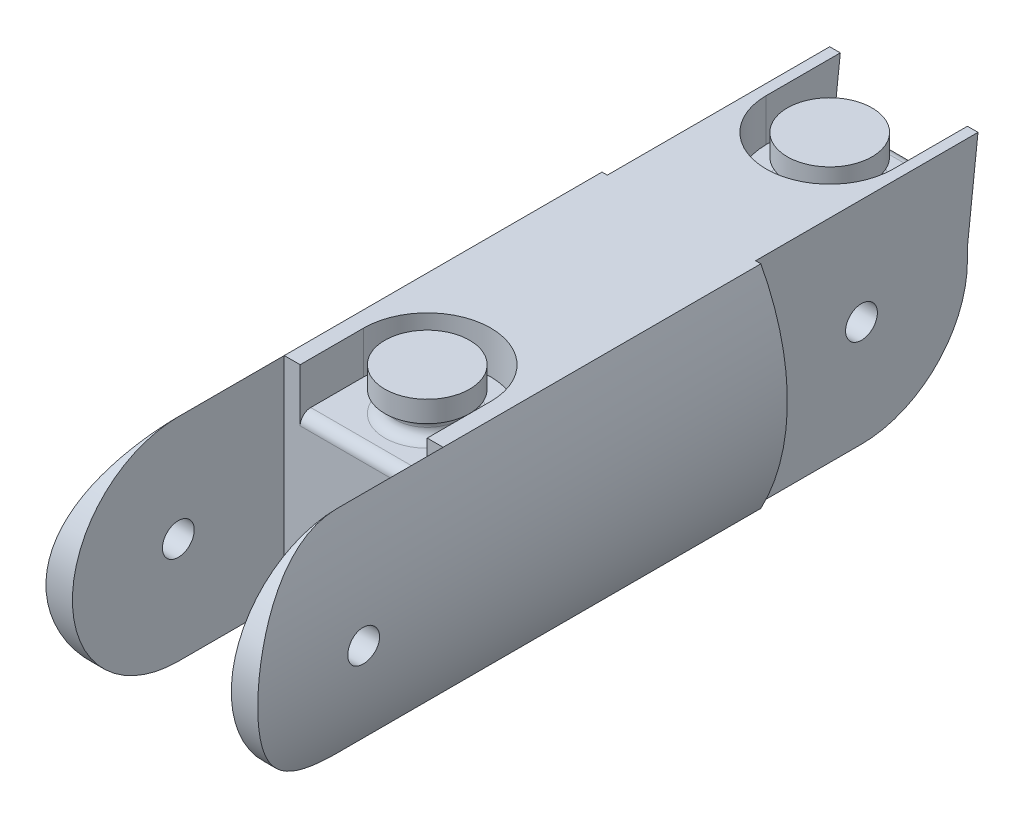
SolidWorks part; units mm, degrees
ref_plane "Alzado" through (0, 0, 0) normal (0, 0, 1) x (1, 0, 0)
ref_plane "Planta" through (0, 0, 0) normal (0, 1, 0) x (1, 0, 0)
ref_plane "Vista lateral" through (0, 0, 0) normal (1, 0, 0) x (0, 0, -1)
sketch "Croquis2" plane through (0, 0, 0) normal (0, 0, 1) x (1, 0, 0)
  line L5 (-7.5, -10) -> (7.5, -10)
  line L7 (-7.5, 10) -> (7.5, 10)
  line L9 (-7.5, -10) -> (7.5, 10) construction
  line L10 (-7.5, 10) -> (7.5, -10) construction
  arc A2 (-7.5, 10) -> (-7.5, -10) centre (11.25, 0) ccw
  arc A3 (7.5, -10) -> (7.5, 10) centre (-11.25, 0) ccw
  point P0 (0, 0)
  dimension "D1" = 15
  dimension "D2" = 20
extrude "Saliente-Extruir2" add sketch "Croquis2" along normal blind 50
sketch "Croquis4" plane through (0, 0, 0) normal (0, 0, -1) x (-1, 0, 0)
  line L1 (7.5, -10) -> (-7.5, -10) construction
  circle A0 centre (0, -7) radius 1.5
  dimension "D2" = 3
  dimension "D1" = 3
extrude "Cortar-Extruir1" cut sketch "Croquis4" against normal blind 50
sketch "Croquis3" plane through (0, 0, 0) normal (0, 0, -1) x (-1, 0, 0)
  line L8 (7.5, -10) -> (-7.5, -10) construction
  line L10 (7, 10) -> (7, -10)
  line L11 (7, -10) -> (3, -10)
  line L12 (-7, 10) -> (-7, -10)
  line L13 (7, 10) -> (-7, -10) construction
  line L14 (7, -10) -> (-7, 10) construction
  line L16 (3, -3) -> (3, -10)
  line L17 (-3, -10) -> (-7, -10)
  line L19 (-3, -3) -> (3, -3)
  line L20 (-3, -3) -> (-3, -10)
  line L21 (-7, 10) -> (7, 10)
  point P0 (0, 0)
  dimension "D1" = 14
  dimension "D2" = 4
  dimension "D3" = 4
  dimension "D4" = 7
extrude "Saliente-Extruir3" add sketch "Croquis3" along normal blind 20
sketch "Croquis8" plane through (-7, 0, 0) normal (-1, 0, 0) x (0, 0, 1)
  line L0 (-20, -10) -> (-20, 10) construction
  line L1 (-20, -10) -> (0, -10) construction
  circle A0 centre (-10, 0) radius 1.5
  point P4 (-20, 0)
  dimension "D1" = 3
  dimension "D2" = 10
  dimension "D3" = 10
extrude "Cortar-Extruir4" cut sketch "Croquis8" against normal blind 14
fillet "Redondeo1" radius 10 2 edges at (-5, -10, -20) (5, -10, -20)
sketch "Croquis6" plane through (0, 0, 50) normal (0, 0, 1) x (1, 0, 0)
  line L1 (-7.5, 10) -> (7.5, 10)
  line L2 (-7.5, 10) -> (-7.5, -10)
  line L3 (-7.5, -10) -> (7.5, -10)
  line L4 (7.5, 10) -> (7.5, -10)
extrude "Cortar-Extruir2" cut sketch "Croquis6" against normal blind 20
sketch "Croquis7" plane through (0, 0, 0) normal (1, 0, 0) x (0, 0, -1)
  line L0 (-50, 10) -> (-50, -10) construction
  line L2 (-40, -10) -> (-55, -10)
  line L4 (-40, 10) -> (-55, 10)
  line L5 (-55, -10) -> (-55, 10)
  arc A0 (-40, 10) -> (-40, -10) centre (-40, 0) ccw
  circle A1 centre (-40, 0) radius 1.5
  dimension "D3" = 10
  dimension "D4" = 3
  dimension "D1" = 10
  dimension "D2" = 15
extrude "Cortar-Extruir3" cut sketch "Croquis7" against normal through all both and the other way through all
sketch "Sketch1" plane through (0, 10, 0) normal (0, 1, 0) x (1, 0, 0)
  line L0 (7.5, -30) -> (-7.5, -30) construction
  line L1 (-7, 20) -> (7, 20) construction
  line L4 (-6, 14) -> (-6, 20)
  line L5 (-6, 20) -> (6, 20)
  line L6 (6, 14) -> (6, 20)
  line L8 (-6, -24) -> (-6, -30)
  line L9 (-6, -30) -> (6, -30)
  line L10 (6, -24) -> (6, -30)
  arc A0 (6, -24) -> (-6, -24) centre (0, -24) ccw
  arc A1 (-6, 14) -> (6, 14) centre (0, 14) ccw
  dimension "D1" = 12
  dimension "D2" = 12
  dimension "D3" = 6
  dimension "D4" = 6
extrude "Cut-Extrude1" cut sketch "Sketch1" against normal blind 4
sketch "Sketch2" plane through (0, 6, 0) normal (0, 1, 0) x (1, 0, 0)
  circle A1 centre (0, 14) radius 3
  circle A2 centre (0, -24) radius 3
  dimension "D1" = 6
  dimension "D2" = 6
extrude "Boss-Extrude1" add sketch "Sketch2" along normal blind 2
sketch "Sketch3" plane through (0, 8, 0) normal (0, 1, 0) x (1, 0, 0)
  circle A0 centre (0, -24) radius 4
  circle A1 centre (0, 14) radius 4
  dimension "D1" = 8
  dimension "D2" = 8
extrude "Boss-Extrude2" add sketch "Sketch3" along normal blind 2
fillet "Fillet1" radius 1 4 edges at (0, 8, -11) (0, 6, -11) (0, 8, 27) (0, 6, 27)
fillet "Fillet2" radius 1 2 edges at (0, 6, 30) (0, 6, -20)
fillet "Fillet3" radius 1 2 edges at (1.5, -7, 30) (-1.5, -7, 0)
sketch "Sketch4" plane through (7, 0, 0) normal (1, 0, 0) x (0, 0, -1)
  line L0 (20, 10) -> (21, 10)
  line L1 (21, 10) -> (19.5394, -3)
  line L2 (19.5394, -3) -> (20, 10)
  dimension "D1" = 1
sketch "Sketch5" plane through (-7, 0, 0) normal (-1, 0, 0) x (0, 0, 1)
  line L0 (-20, 10) -> (-21, 10)
  line L1 (-21, 10) -> (-19.5394, -3)
  line L2 (-19.5394, -3) -> (-20, 10)
extrude "Boss-Extrude3" add sketch "Sketch4" against normal blind 1
extrude "Boss-Extrude4" add sketch "Sketch5" against normal blind 1
sketch "Sketch6" plane through (0, 0, 0) normal (0, 0, 1) x (1, 0, 0)
  line L1 (-3, -2) -> (3, -2)
  line L3 (-3, -4) -> (3, -4)
  line L5 (-7.5, 10) -> (-7.5, -10) construction
  line L8 (-7.5, -10) -> (7.5, -10) construction
  arc A0 (-3, -2) -> (-3, -4) centre (-3, -3) ccw
  arc A1 (3, -4) -> (3, -2) centre (3, -3) ccw
  dimension "D1" = 6
  dimension "D2" = 4.5
  dimension "D4" = 8
extrude "Cut-Extrude2" cut sketch "Sketch6" against normal blind 60 from offset 28
sketch "Sketch7" plane through (0, -10, 0) normal (0, -1, 0) x (1, 0, 0)
  line L0 (7, -20) -> (-7, -20) construction
  line L1 (-4, 0.014) -> (4, 0.014)
  line L2 (-4, 0.014) -> (-4, -20)
  line L3 (-4, -20) -> (4, -20)
  line L4 (4, 0.014) -> (4, -20)
  line L5 (-7, -10) -> (-7, -20) construction
  dimension "D1" = 8
  dimension "D2" = 3
extrude "Cut-Extrude3" cut sketch "Sketch7" against normal blind 7
fillet "Fillet4" radius 0.5 3 edges at (3.7071, -3.7071, 0.014) (-3.7071, -3.7071, 0.014) (0, -4, 0.014)
